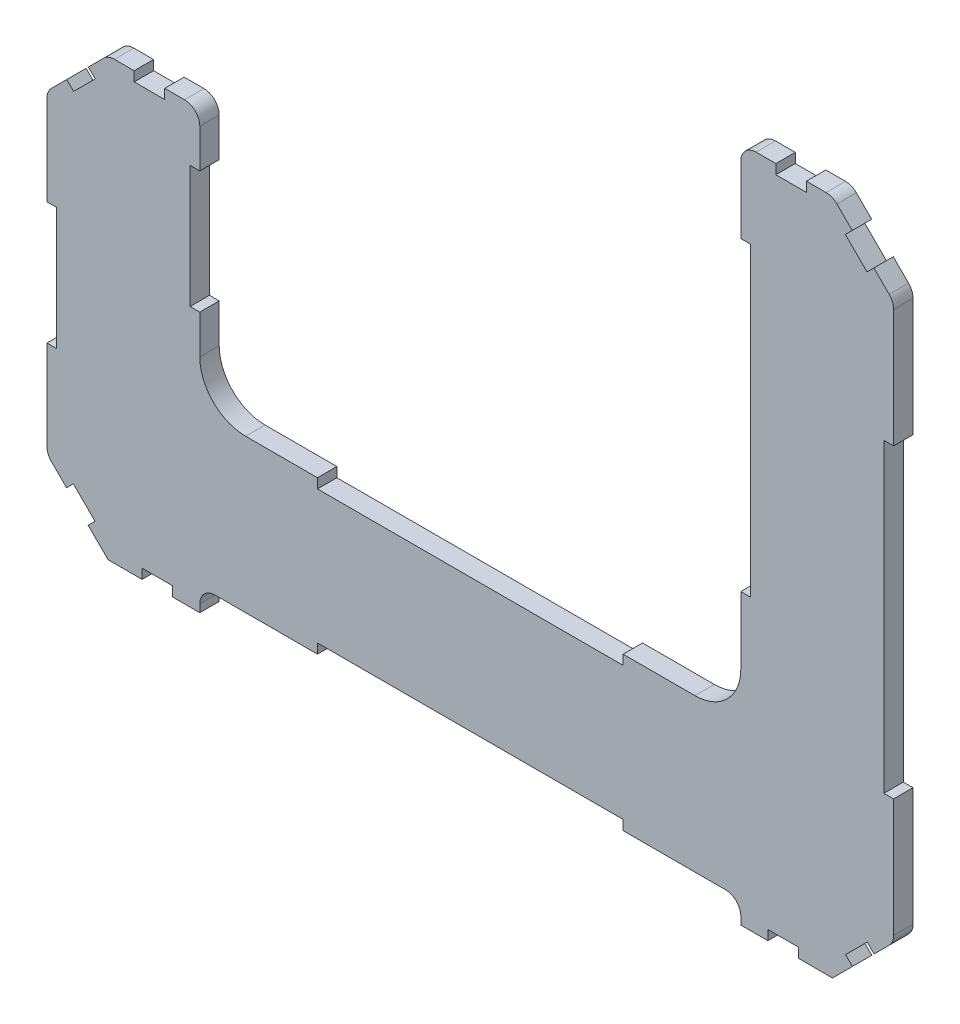
SolidWorks part; units mm, degrees
ref_plane "Front Plane" through (0, 0, 0) normal (0, 0, 1) x (1, 0, 0)
ref_plane "Top Plane" through (0, 0, 0) normal (0, 1, 0) x (1, 0, 0)
ref_plane "Right Plane" through (0, 0, 0) normal (1, 0, 0) x (0, 0, -1)
sketch "Sketch2" plane through (0, 0, 0) normal (0, 0, 1) x (1, 0, 0)
  line L0 (-138.5, 85.3385) -> (-88.5, 85.3385)
  line L1 (-88.5, 85.3385) -> (-88.5, 0)
  line L2 (-88.5, 0) -> (88.5, 0)
  line L3 (88.5, 0) -> (88.5, 164)
  line L4 (88.5, 164) -> (138.5, 164)
  line L5 (138.5, 164) -> (138.5, -57.5)
  line L6 (138.5, -57.5) -> (88.5, -57.5)
  line L7 (88.5, -57.5) -> (88.5, -50)
  line L8 (88.5, -50) -> (-88.5, -50)
  line L9 (-88.5, -50) -> (-88.5, -57.5)
  line L10 (-88.5, -57.5) -> (-138.5, -57.5)
  line L11 (-138.5, -57.5) -> (-138.5, 85.3385)
  line L12 (-33.5, 0) -> (-33.5, 124) construction
  point P10 (-33.5, 0)
  point P14 (88.5, 124)
  point P15 (-33.5, 85.3385)
  dimension "D1" = 124
  dimension "D2" = 122
  dimension "D3" = 55
  dimension "D4" = 40
  dimension "D5" = 50
  dimension "D6" = 50
  dimension "D7" = 7.5
extrude "Boss-Extrude1" add sketch "Sketch2" along normal blind 3.175 and the other way blind 3.175
chamfer "Chamfer1" distance 20 angle 45 4 edges at (-138.5, -57.5, 0) (138.5, -57.5, 0) (138.5, 164, 0) (-138.5, 85.3385, 0)
fillet "Fillet1" radius 15 2 edges at (88.5, 0, 0) (-88.5, 0, 0)
fillet "Fillet2" radius 5 10 edges at (138.5, -37.5, 0) (88.5, -50, 0) (-88.5, -50, 0) (-138.5, -37.5, 0) (-138.5, 65.3385, 0) (-118.5, 85.3385, 0) (-88.5, 85.3385, 0) (138.5, 144, 0) (118.5, 164, 0) (88.5, 164, 0)
sketch "Sketch3" plane through (0, 0, 3.175) normal (0, 0, 1) x (1, 0, 0)
  line L0 (-94.6381, 69.9757) -> (-94.6381, 14.7992)
  line L1 (-94.6381, 14.7992) -> (-97.8131, 14.7992)
  line L2 (-97.8131, 14.7992) -> (-97.8131, 69.9757)
  line L3 (-97.8131, 69.9757) -> (-94.6381, 69.9757)
  line L4 (-127.4635, 65.4691) -> (-114.3536, 78.579)
  line L5 (-114.3536, 78.579) -> (-112.1085, 76.3339)
  line L6 (-112.1085, 76.3339) -> (-125.2184, 63.2241)
  line L7 (-125.2184, 63.2241) -> (-127.4635, 65.4691)
  line L8 (-129.3392, 54.7846) -> (-126.1642, 54.7846)
  line L9 (-126.1642, 54.7846) -> (-126.1642, -28.3138)
  line L10 (-126.1642, -28.3138) -> (-129.3392, -28.3138)
  line L11 (-129.3392, -28.3138) -> (-129.3392, 54.7846)
  line L12 (-127.4635, -37.1329) -> (-125.2184, -34.8879)
  line L13 (-125.2184, -34.8879) -> (-110.9382, -49.1681)
  line L14 (-110.9382, -49.1681) -> (-113.1832, -51.4132)
  line L15 (-113.1832, -51.4132) -> (-127.4635, -37.1329)
  line L16 (-67.7784, -44.3183) -> (-67.7784, -41.1433)
  line L17 (-67.7784, -41.1433) -> (53.0181, -41.1433)
  line L18 (53.0181, -41.1433) -> (53.0181, -44.3183)
  line L19 (53.0181, -44.3183) -> (-67.7784, -44.3183)
  line L20 (114.9313, -49.5303) -> (117.1763, -51.7753)
  line L21 (117.1763, -51.7753) -> (131.7883, -37.1634)
  line L22 (131.7883, -37.1634) -> (129.5432, -34.9183)
  line L23 (129.5432, -34.9183) -> (114.9313, -49.5303)
  line L24 (-67.7784, -4.1746) -> (-67.7784, -7.3496)
  line L25 (-67.7784, -7.3496) -> (63.5847, -7.3496)
  line L26 (63.5847, -7.3496) -> (63.5847, -4.1746)
  line L27 (63.5847, -4.1746) -> (-67.7784, -4.1746)
  line L28 (92.7516, 20.9162) -> (91.2159, 151.9937)
  line L29 (91.2159, 151.9937) -> (94.3909, 151.9937)
  line L30 (94.3909, 151.9937) -> (95.9266, 20.9162)
  line L31 (95.9266, 20.9162) -> (92.7516, 20.9162)
  line L32 (96.8341, 161.8762) -> (96.8341, 158.7012)
  line L33 (96.8341, 158.7012) -> (112.5649, 158.7012)
  line L34 (112.5649, 158.7012) -> (112.5649, 161.8762)
  line L35 (112.5649, 161.8762) -> (96.8341, 161.8762)
  line L37 (117.7781, 156.4535) -> (120.0231, 158.6985)
  line L38 (120.0231, 158.6985) -> (133.8694, 144.8523)
  line L39 (133.8694, 144.8523) -> (131.6243, 142.6072)
  line L40 (131.6243, 142.6072) -> (117.7781, 156.4535)
  line L41 (129.9213, 134.1701) -> (133.0963, 134.1701)
  line L42 (133.0963, 134.1701) -> (133.0963, -24.961)
  line L43 (133.0963, -24.961) -> (129.9213, -24.961)
  line L44 (129.9213, -24.961) -> (129.9213, 134.1701)
  line L45 (118.5, -57.5) -> (137.0355, -38.9645) construction
  line L46 (-137.0355, -38.9645) -> (-118.5, -57.5) construction
  line L47 (-119.9645, 83.874) -> (-137.0355, 66.8029) construction
  line L48 (137.0355, 145.4645) -> (119.9645, 162.5355) construction
  dimension "D1" = 3.175
extrude "Cut-Extrude1" [suppressed] cut sketch "Sketch3" against normal through all
sketch "magnets" plane through (0, 0, 3.175) normal (0, 0, 1) x (1, 0, 0)
  point P0 (94.6751, 158.4052)
  point P1 (114.7572, -50)
  point P2 (131.9288, 140.6094)
  point P3 (131.9288, -32.8111)
  point P4 (0, -44.1618)
  point P5 (-114.0039, -50)
  point P6 (-130.8821, -32.8111)
  point P9 (-130.8821, 62.3605)
  point P10 (-93.5499, 79.7316)
  point P12 (0, -4.7392)
sketch "Sketch4" plane through (0, 0, 3.175) normal (0, 0, 1) x (1, 0, 0)
  line L0 (99.9645, 164) -> (99.9645, 160.825)
  line L1 (116.4289, 164) -> (93.5, 164) construction
  line L2 (99.9645, 160.825) -> (109.9645, 160.825)
  line L3 (109.9645, 160.825) -> (109.9645, 164)
  line L4 (124.9645, 157.5355) -> (122.7194, 155.2905)
  line L5 (137.0355, 145.4645) -> (119.9645, 162.5355) construction
  line L6 (122.7194, 155.2905) -> (129.7905, 148.2194)
  line L7 (129.7905, 148.2194) -> (132.0355, 150.4645)
  line L8 (88.5, 137) -> (91.675, 137)
  line L9 (88.5, 159) -> (88.5, 15) construction
  line L10 (91.675, 137) -> (91.675, 37)
  line L11 (91.675, 37) -> (88.5, 37)
  line L12 (138.5, 103.25) -> (135.325, 103.25)
  line L13 (138.5, -35.4289) -> (138.5, 141.9289) construction
  line L14 (135.325, 103.25) -> (135.325, 3.25)
  line L15 (135.325, 3.25) -> (138.5, 3.25)
  line L16 (-50, 0) -> (-50, -3.175)
  line L17 (73.5, 0) -> (-73.5, 0) construction
  line L18 (-50, -3.175) -> (50, -3.175)
  line L19 (50, -3.175) -> (50, 0)
  line L20 (-50, -50) -> (-50, -46.825)
  line L21 (-83.5, -50) -> (83.5, -50) construction
  line L22 (-50, -46.825) -> (50, -46.825)
  line L23 (50, -46.825) -> (50, -50)
  line L24 (-135.325, -6.0808) -> (-138.5, -6.0808)
  line L25 (-138.5, 63.2674) -> (-138.5, -35.4289) construction
  line L26 (-135.325, 33.9192) -> (-135.325, -6.0808)
  line L27 (-135.325, 33.9192) -> (-138.5, 33.9192)
  line L28 (-132.0355, 71.8029) -> (-129.7905, 69.5579)
  line L29 (-119.9645, 83.874) -> (-137.0355, 66.8029) construction
  line L30 (-129.7905, 69.5579) -> (-122.7194, 76.6289)
  line L31 (-122.7194, 76.6289) -> (-124.9645, 78.874)
  line L32 (-109.9645, 85.3385) -> (-109.9645, 82.1635)
  line L33 (-93.5, 85.3385) -> (-116.4289, 85.3385) construction
  line L35 (-109.9645, 82.1635) -> (-99.9645, 82.1635)
  line L36 (-88.5, 67.6692) -> (-91.675, 67.6692)
  line L37 (-88.5, 15) -> (-88.5, 80.3385) construction
  line L38 (-91.675, 67.6692) -> (-91.675, 27.6692)
  line L39 (-91.675, 27.6692) -> (-88.5, 27.6692)
  line L40 (-107.375, -57.5) -> (-107.375, -54.325)
  line L41 (-118.5, -57.5) -> (-88.5, -57.5) construction
  line L42 (-107.375, -54.325) -> (-97.375, -54.325)
  line L43 (-97.375, -54.325) -> (-97.375, -57.5)
  line L44 (97.375, -57.5) -> (97.375, -54.325)
  line L45 (88.5, -57.5) -> (118.5, -57.5) construction
  line L46 (97.375, -54.325) -> (107.375, -54.325)
  line L47 (107.375, -54.325) -> (107.375, -57.5)
  line L48 (-132.0988, -43.9012) -> (-129.8537, -41.6561)
  line L49 (-137.0355, -38.9645) -> (-118.5, -57.5) construction
  line L50 (-129.8537, -41.6561) -> (-122.7827, -48.7272)
  line L51 (-122.7827, -48.7272) -> (-125.0277, -50.9723)
  line L52 (125.0277, -50.9723) -> (122.7827, -48.7272)
  line L53 (118.5, -57.5) -> (137.0355, -38.9645) construction
  line L54 (122.7827, -48.7272) -> (129.8537, -41.6561)
  line L55 (129.8537, -41.6561) -> (132.0988, -43.9012)
  line L56 (-128.5633, -47.4367) -> (-126.3182, -45.1917) construction
  line L57 (-102.375, -57.5) -> (-102.375, -54.325)
  line L58 (102.375, -57.5) -> (102.375, -54.325)
  line L59 (-128.5, 75.3385) -> (-126.2549, 73.0934) construction
  line L60 (-104.9645, 82.1635) -> (-104.9645, 85.3385) construction
  line L61 (126.2549, 151.7549) -> (128.5, 154) construction
  line L62 (126.3182, -45.1917) -> (128.5633, -47.4367) construction
  line L63 (88.5, -57.5) -> (116.25, -57.5) construction
  line L64 (120.091, -55.909) -> (137.0355, -38.9645) construction
  line L65 (120.091, -55.909) -> (118.5, -57.5) construction
  line L66 (118.5, -57.5) -> (116.25, -57.5) construction
  line L67 (-88.5, -57.5) -> (-116.25, -57.5) construction
  line L68 (-116.25, -57.5) -> (-118.5, -57.5) construction
  line L69 (-118.5, -57.5) -> (-120.091, -55.909) construction
  line L70 (-120.091, -55.909) -> (-137.0355, -38.9645) construction
  line L71 (-99.9645, 82.1635) -> (-99.9645, 85.3385)
  point P95 (0, -46.825)
  point P97 (0, -50)
  point P99 (0, -3.175)
  point P101 (135.325, 53.25)
  point P103 (138.5, 53.25)
  point P104 (91.675, 87)
  point P105 (88.5, 87)
  point P106 (104.9645, 160.825)
  point P107 (104.9645, 164)
  point P108 (128.5, 154)
  point P109 (126.2549, 151.7549)
  point P112 (-135.325, 13.9192)
  point P113 (-138.5, 13.9192)
  point P114 (-91.675, 47.6692)
  point P115 (-88.5, 47.6692)
  point P116 (126.3182, -45.1917)
  point P117 (127.7678, -48.2322)
  line M1 (118.5, -57.5) -> (137.0355, -38.9645)
  line M3 (138.5, -35.4289) -> (138.5, 141.9289)
  line M5 (137.0355, 145.4645) -> (119.9645, 162.5355)
  line M7 (116.4289, 164) -> (93.5, 164)
  line M9 (88.5, 159) -> (88.5, 15)
  line M11 (73.5, 0) -> (-73.5, 0)
  line M13 (-88.5, 15) -> (-88.5, 80.3385)
  line M15 (-93.5, 85.3385) -> (-116.4289, 85.3385)
  line M17 (-119.9645, 83.874) -> (-137.0355, 66.8029)
  line M19 (-138.5, 63.2674) -> (-138.5, -35.4289)
  line M21 (-137.0355, -38.9645) -> (-118.5, -57.5)
  line M22 (-118.5, -57.5) -> (-88.5, -57.5)
  line M25 (-83.5, -50) -> (83.5, -50)
  line M28 (88.5, -57.5) -> (118.5, -57.5)
  dimension "D1" = 3.175
  dimension "D5" = 100
  dimension "D6" = 100
  dimension "D7" = 100
  dimension "D8" = 100
  dimension "D4" = 10
  dimension "D2" = 10
  dimension "D10" = 2.25
  dimension "D3" = 2.25
  dimension "D11" = 10
  dimension "D13" = 3.175
  dimension "D12" = 10
  dimension "D14" = 10
  dimension "D15" = 10
  dimension "D16" = 10
  dimension "D17" = 10
  dimension "D18" = 40
  dimension "D19" = 3.175
extrude "wall_slots" cut sketch "Sketch4" against normal blind 60 contours L26 L27 L24 M19 | L18 L19 L16 M11 | L23 L22 L20 M25 | L51 L50 L48 M21 | L57 L43 L42 M22 | L57 L42 L40 M22 | L38 L39 L36 M13 | L35 L71 L32 M15 | L30 L31 L28 M17 | L58 L47 L46 M28 | L58 L46 L44 M28 | L55 L54 L52 M1 | L14 L15 L12 M3 | L11 L10 L8 M9 | L2 L3 L0 M7 | L6 L7 L4 M5 region at (104.9645, 162.4125, 3.175) region at (127.3775, 152.8775, 3.175) region at (90.0875, 87, 3.175) region at (136.9125, 53.25, 3.175) region at (0, -1.5875, 3.175) region at (0, -48.4125, 3.175) region at (-136.9125, 13.9192, 3.175) region at (-127.3775, 74.2159, 3.175) region at (-104.9645, 83.751, 3.175) region at (-90.0875, 47.6692, 3.175) region at (-127.4407, -46.3142, 3.175) region at (-104.875, -55.9125, 3.175) region at (-99.875, -55.9125, 3.175) region at (127.4407, -46.3142, 3.175) region at (99.875, -55.9125, 3.175) region at (104.875, -55.9125, 3.175)
sketch "wall_measure" plane through (0, 0, 3.175) normal (0, 0, 1) x (1, 0, 0)
  line L0 (-116.4289, 85.3385) -> (-116.4289, 82.1635)
  line L1 (-116.4289, 82.1635) -> (-93.5, 82.1635)
  line L2 (-93.5, 82.1635) -> (-93.5, 85.3385)
  line L4 (93.5, 164) -> (93.5, 160.825)
  line L5 (93.5, 160.825) -> (116.4289, 160.825)
  line L6 (116.4289, 160.825) -> (116.4289, 164)
  line L7 (99.9645, 160.825) -> (109.9645, 160.825) construction
  line L8 (119.9645, 162.5355) -> (117.7194, 160.2905)
  line L9 (117.7194, 160.2905) -> (134.7905, 143.2194)
  line L10 (134.7905, 143.2194) -> (137.0355, 145.4645)
  line L11 (137.0355, 145.4645) -> (132.0355, 150.4645) construction
  line L12 (88.5, 159) -> (91.675, 159)
  line L13 (91.675, 159) -> (91.675, 15)
  line L14 (91.675, 15) -> (88.5, 15)
  line L15 (88.5, 37) -> (88.5, 15) construction
  line L16 (138.5, 141.9289) -> (135.325, 141.9289)
  line L17 (135.325, 141.9289) -> (135.325, -35.4289)
  line L18 (135.325, -35.4289) -> (138.5, -35.4289)
  line L19 (-73.5, 0) -> (-73.5, -3.175)
  line L20 (-73.5, -3.175) -> (73.5, -3.175)
  line L21 (73.5, -3.175) -> (73.5, 0)
  line L22 (-83.5, -50) -> (-83.5, -46.825)
  line L23 (-83.5, -46.825) -> (83.5, -46.825)
  line L24 (83.5, -46.825) -> (83.5, -50)
  line L25 (88.5, -55) -> (116.2868, -55)
  line L26 (116.2868, -55) -> (116.2868, -57.5)
  line L27 (137.0355, -38.9645) -> (134.7905, -36.7194)
  line L28 (134.7905, -36.7194) -> (117.8199, -53.69)
  line L29 (117.8199, -53.69) -> (120.065, -55.935)
  line L30 (118.5, -57.5) -> (125.0277, -50.9723) construction
  line L31 (122.7827, -48.7272) -> (129.8537, -41.6561) construction
  line L32 (116.2868, -57.5) -> (118.5, -57.5) construction
  line L33 (118.5, -57.5) -> (120.065, -55.935) construction
  line L34 (-138.5, 63.2674) -> (-133.5, 63.2674)
  line L35 (-133.5, 63.2674) -> (-133.5, -35.4289)
  line L36 (-133.5, -35.4289) -> (-138.5, -35.4289)
  line L37 (-88.5, 80.3385) -> (-91.675, 80.3385)
  line L38 (-91.675, 80.3385) -> (-91.675, 15)
  line L39 (-91.675, 15) -> (-88.5, 15)
  line L40 (-50, -46.825) -> (50, -46.825) construction
  line L41 (-50, -3.175) -> (50, -3.175) construction
  line L42 (135.325, 103.25) -> (135.325, 3.25) construction
  line L43 (91.675, 137) -> (91.675, 37) construction
  line L44 (122.7194, 155.2905) -> (129.7905, 148.2194) construction
  line L45 (-91.675, 67.6692) -> (-91.675, 27.6692) construction
  line L47 (-109.9645, 82.1635) -> (-99.9645, 82.1635) construction
  arc A0 (73.5, 0) -> (88.5, 15) centre (73.5, 15) ccw construction
  arc A1 (-88.5, 15) -> (-73.5, 0) centre (-73.5, 15) ccw construction
  dimension "D1" = 22.9289
  dimension "D2" = 22.9289
  dimension "D3" = 24.1421
  dimension "D4" = 144
  dimension "D5" = 177.3579
  dimension "D6" = 147
  dimension "D7" = 167
  dimension "D8" = 24
  dimension "D9" = 2.2132
  dimension "D10" = 27.7868
  dimension "D11" = 98.6963
  dimension "D12" = 65.3385
equation "\"dX\"= 122mm"
equation "\"dY\"= 124mm"
equation "\"hmotor\"= 50mm"
equation "\"D1@Sketch2\"=\"dY\""
equation "\"D2@Sketch2\"=\"dX\""
equation "\"D5@Sketch2\"=\"hmotor\""
equation "\"D6@Sketch2\"=\"hmotor\""
equation "\"t_wood\"= 0.25in"
equation "\"D1@Boss-Extrude1\"=\"t_wood\"/2"
equation "\"D2@Boss-Extrude1\"=\"t_wood\"/2"
equation "\"D1@Sketch3\"=\"t_wood\"/2"
equation "\"D1@Sketch4\"=\"t_wood\"/2"
equation "\"D13@Sketch4\"=\"t_wood\"/2"
equation "\"D19@Sketch4\"=\"t_wood\"/2"
